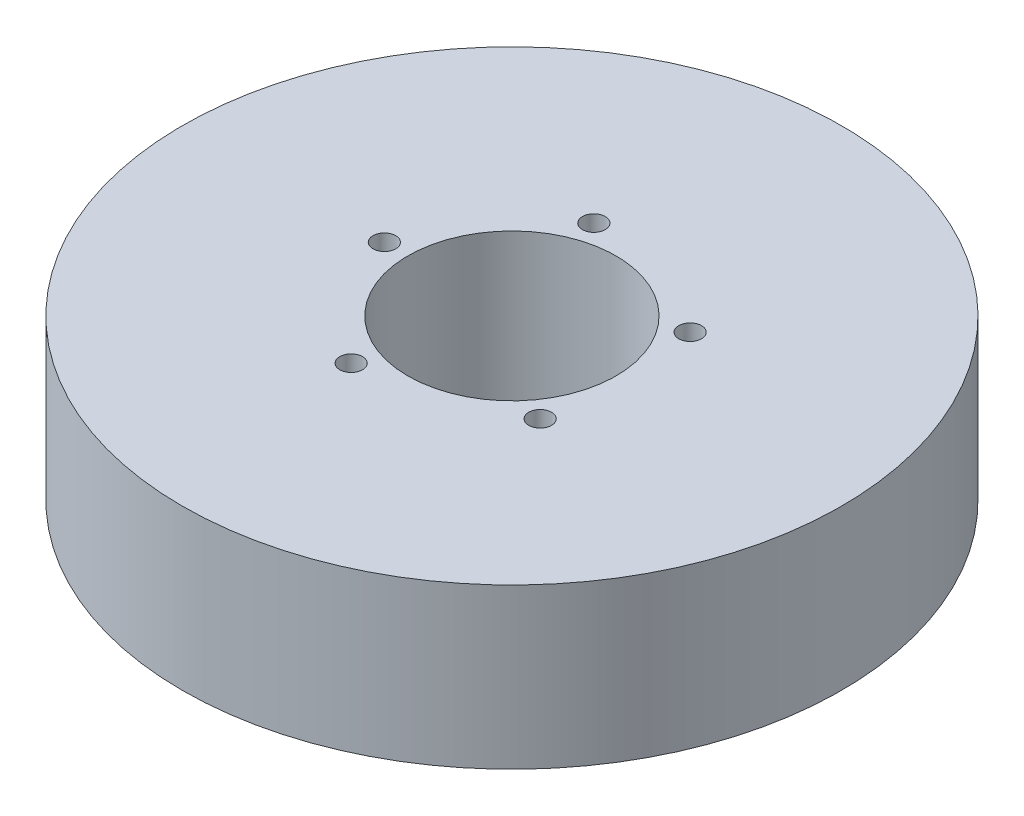
SolidWorks part; units mm, degrees
ref_plane "Front Plane" through (0, 0, 0) normal (0, 0, 1) x (1, 0, 0)
ref_plane "Top Plane" through (0, 0, 0) normal (0, 1, 0) x (1, 0, 0)
ref_plane "Right Plane" through (0, 0, 0) normal (1, 0, 0) x (0, 0, -1)
sketch "Sketch1" plane through (0, 0, 0) normal (0, 1, 0) x (1, 0, 0)
  circle A0 centre (0, 0) radius 47.5
  dimension "FLANGE_OD" = 95
extrude "Boss-Extrude1" add sketch "Sketch1" along normal blind 23
sketch "Sketch2" plane through (0, 0, 0) normal (0, 1, 0) x (1, 0, 0)
  circle A0 centre (0, 0) radius 15
  dimension "BORE_D" = 30
extrude "Cut-Extrude1" cut sketch "Sketch2" along normal through all
sketch "Sketch3" plane through (0, 23, 0) normal (0, 1, 0) x (1, 0, 0)
  circle A0 centre (0, 0) radius 18.389 construction
  circle A1 centre (-18.389, 0) radius 1.6433
  dimension "BOLT_D" = 3.2866
  dimension "BOLT_PCD" = 36.7781
extrude "Cut-Extrude2" cut sketch "Sketch3" against normal blind 19.9981
pattern_circular "CirPattern1" count 5 over 360 about axis through (0, 0, 0) along (0, 1, 0) of "Cut-Extrude2"
